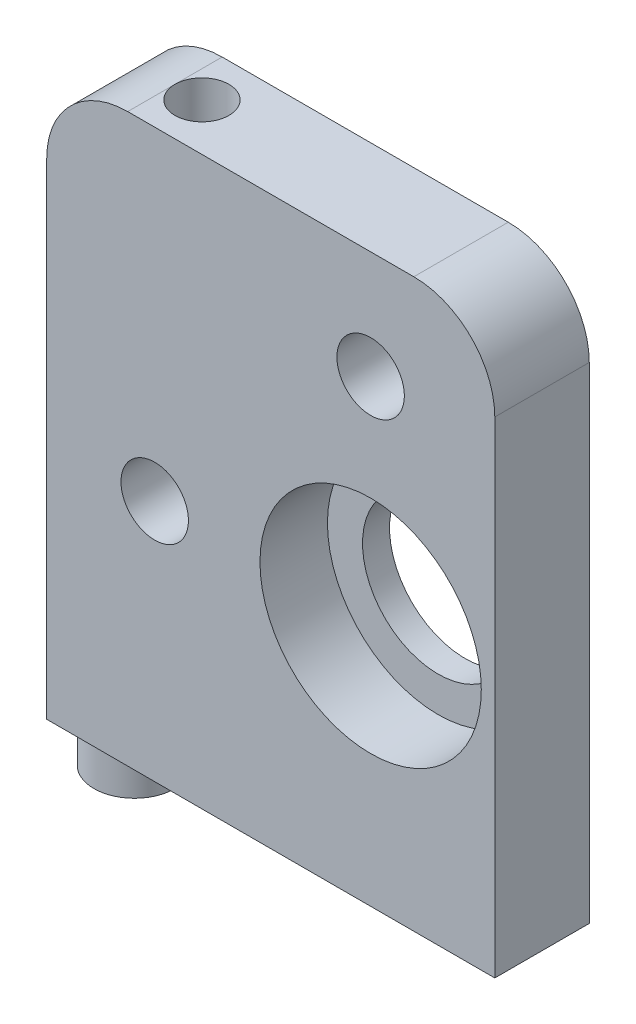
SolidWorks part; units mm, degrees
ref_plane "前视基准面" through (0, 0, 0) normal (0, 0, 1) x (1, 0, 0)
ref_plane "上视基准面" through (0, 0, 0) normal (0, 1, 0) x (1, 0, 0)
ref_plane "右视基准面" through (0, 0, 0) normal (1, 0, 0) x (0, 0, -1)
other "Configuration Table"
sketch "草图1" plane through (0, 0, 0) normal (0, 0, 1) x (1, 0, 0)
  line L1 (-12, 12) -> (4.6, 12)
  line L2 (-12, 12) -> (-12, -9)
  line L3 (-12, -9) -> (4.6, -9)
  line L4 (4.6, 12) -> (4.6, -9)
  circle A0 centre (0, 0) radius 2.8
  circle A1 centre (0, 0) radius 4.1
  circle A2 centre (0, 8) radius 1.25
  circle A3 centre (-8, 0) radius 1.25
  dimension "D1" = 5.6
  dimension "D2" = 8.2
  dimension "D7" = 2.5
  dimension "D9" = 2.5
  dimension "D3" = 12
  dimension "D4" = 12
  dimension "D5" = 9
  dimension "D6" = 4.6
  dimension "D8" = 8
  dimension "D10" = 8
extrude "凸台-拉伸1" add sketch "草图1" along normal blind 3.5 contours L4 L1 L2 L3 A3 A2 A1 region at (-4.373, 1.6912, 0)
extrude "凸台-拉伸2" add sketch "草图1<3>" along normal blind 1 contours A1 A0 region at (-3.984, 0, 0)
sketch "草图1<3>" plane through (0, 0, 0) normal (0, 0, 1) x (1, 0, 0) same geometry as "草图1"
fillet "圆角1" radius 3 1 edges at (-12, 12, 1.75)
fillet "圆角2" radius 3 1 edges at (4.6, 12, 1.75)
sketch "草图2" plane through (0, -9, 0) normal (0, -1, 0) x (1, 0, 0)
  line L0 (-12, 0) -> (4.6, 0) construction
  line L3 (-12, 3.5) -> (-12, 0) construction
  circle A0 centre (-10.5, 1.75) radius 1.5
  circle A2 centre (-4.5, 1.75) radius 1
  dimension "D1" = 3
  dimension "D3" = 4.5
  dimension "D4" = 2
  dimension "D2" = 1.75
  dimension "D5" = 6
extrude "切除-拉伸1" cut sketch "草图2" against normal blind 6 contours A2 region at (-4.5, -9, 1.75)
extrude "凸台-拉伸3" add sketch "草图2<3>" along normal blind 1.6 contours A0 region at (-10.5, -9, 1.75)
sketch "草图2<3>" plane through (0, -9, 0) normal (0, -1, 0) x (1, 0, 0) same geometry as "草图2"
sketch "草图3" plane through (0, 12, 0) normal (0, 1, 0) x (1, 0, 0)
  line L0 (-9, 0) -> (1.6, 0) construction
  circle A0 centre (-8, -1.75) radius 1
  dimension "D2" = 2
  dimension "D3" = 1.75
  dimension "D1" = 8
extrude "切除-拉伸2" cut sketch "草图3" against normal blind 6
